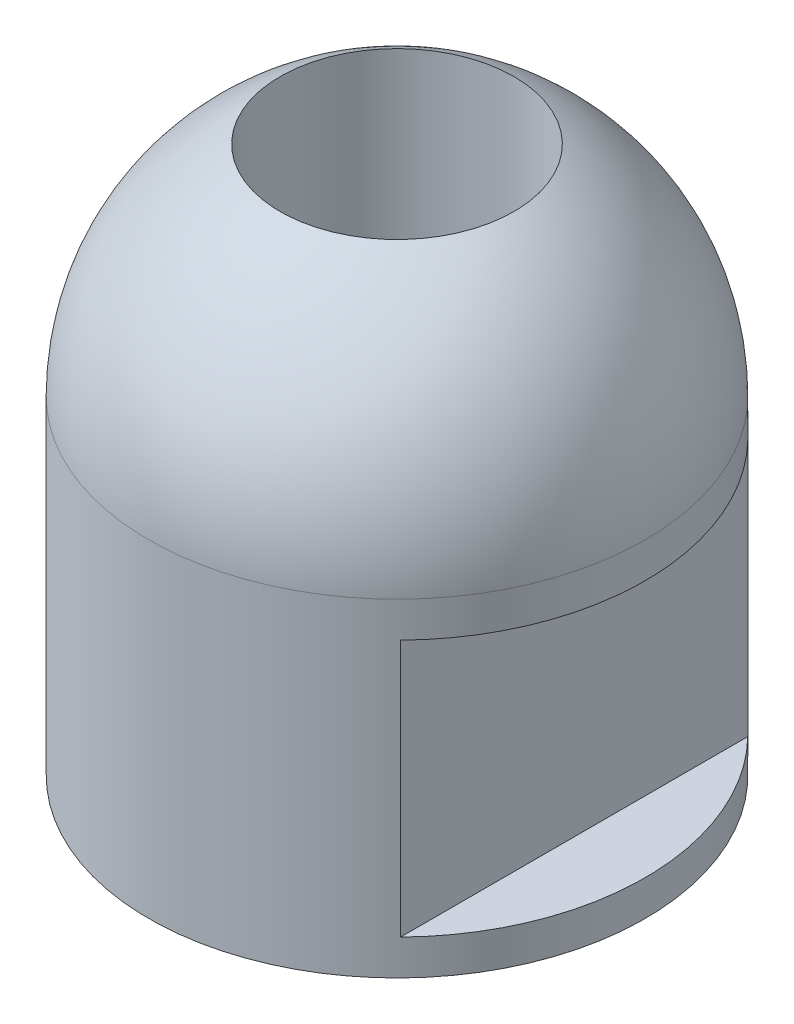
SolidWorks part; units mm, degrees
ref_plane "Front Plane" through (0, 0, 0) normal (0, 0, 1) x (1, 0, 0)
ref_plane "Top Plane" through (0, 0, 0) normal (0, 1, 0) x (1, 0, 0)
ref_plane "Right Plane" through (0, 0, 0) normal (1, 0, 0) x (0, 0, -1)
sketch "Sketch1" plane through (0, 0, 0) normal (0, 0, 1) x (1, 0, 0)
  line L0 (0, 0) -> (0, 8.1277)
  line L1 (0, 0) -> (3.5, 0)
  line L2 (3.5, 0) -> (3.5, 4.6277)
  line L4 (0, 8.1277) -> (0, 11.2857) construction
  line L5 (0, 7.5) -> (2, 7.5) construction
  arc A0 (3.5, 4.6277) -> (0, 8.1277) centre (0, 4.6277) ccw
  point P9 (1.9801, 6.886)
  point P10 (0, 6.8478)
  dimension "D1" = 3.5
  dimension "D2" = 7.5
  dimension "D3" = 4
revolve "Revolve1" add sketch "Sketch1" angle 360 about L4
sketch "Sketch4" plane through (0, 0, 0) normal (0, -1, 0) x (-1, 0, 0)
  point P0 (0, 0)
hole_wizard "Tap Drill for M4x0.7 Tap1" positions "Sketch4" profile "Sketch3" hole size "M4x0.7" standard "ANSI Metric" end condition through all
sketch "Sketch3" plane through (0, 0, 0) normal (1, 0, 0) x (0, 0, -1)
  line L0 (0, 0) -> (0, 8.1277)
  line L1 (0, 8.1277) -> (1.65, 8.1277)
  line L2 (1.65, 8.1277) -> (1.65, 0)
  line L5 (1.65, 0) -> (0, 0)
  line L11 (0, -6.35) -> (0, 107.95) construction
  dimension "Thru Hole Dia." = 3.3
  dimension "Thru Hole Depth" = 8.1277
sketch "Sketch5" plane through (0, 0, 0) normal (0, 0, 1) x (1, 0, 0)
  line L0 (3.5, 0.5) -> (2.5, 0.5)
  line L1 (3.5, 0) -> (3.5, 4.6277) construction
  line L2 (2.5, 0.5) -> (2.5, 4.1277)
  line L3 (2.5, 4.1277) -> (3.5, 4.1277)
  line L4 (3.5, 4.1277) -> (3.5, 0.5)
  line L5 (0, 0) -> (0, 8.9579) construction
  line L6 (-3.5, 0) -> (3.5, 0) construction
  line L7 (3.5, 4.6277) -> (-3.5, 4.6277) construction
  line L8 (-3.5, 4.1277) -> (-3.5, 0.5)
  line L9 (-2.5, 4.1277) -> (-3.5, 4.1277)
  line L10 (-2.5, 0.5) -> (-2.5, 4.1277)
  line L11 (-3.5, 0.5) -> (-2.5, 0.5)
  dimension "D1" = 5
  dimension "D2" = 0.5
  dimension "D3" = 0.5
extrude "Cut-Extrude1" cut sketch "Sketch5" against normal through all both and the other way through all
